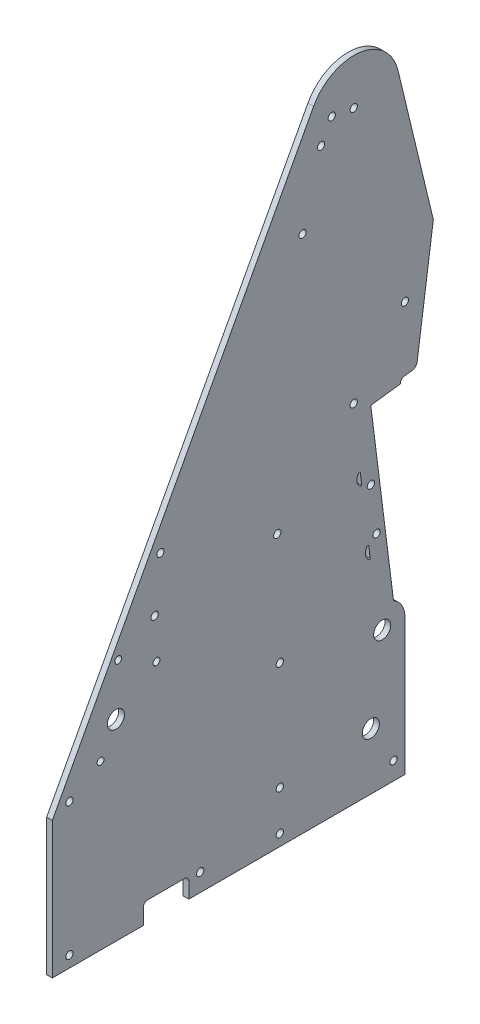
SolidWorks part; units mm, degrees
ref_plane "Front Plane" through (0, 0, 0) normal (0, 0, 1) x (1, 0, 0)
ref_plane "Top Plane" through (0, 0, 0) normal (0, 1, 0) x (1, 0, 0)
ref_plane "Right Plane" through (0, 0, 0) normal (1, 0, 0) x (0, 0, -1)
sketch "Sketch1" plane through (0, 0, 0) normal (1, 0, 0) x (0, 0, -1)
  line L0 (0, 0) -> (0, 76.2)
  line L6 (-19.05, 188.0016) -> (-2.512, 190.0852)
  line L7 (6.4943, 193.62) -> (15.875, 260.35)
  line L8 (15.875, 260.35) -> (-3.8791, 342.4892)
  line L9 (-50.965, 348.5436) -> (-196.85, 76.2)
  line L10 (-196.85, 0) -> (0, 0)
  line L11 (-196.85, 76.2) -> (-196.85, 0)
  line L12 (-19.05, 188.0016) -> (-6.35, 87.1985)
  line L13 (-0.4471, 192.7455) -> (6.4943, 193.62)
  line L14 (-2.512, 190.0852) -> (-3.1086, 194.8203) construction
  line L15 (-2.512, 190.0852) -> (6.1508, 191.1766) construction
  line L16 (6.1508, 191.1766) -> (6.4943, 193.62) construction
  arc A0 (-3.8791, 342.4892) -> (-50.965, 348.5436) centre (-28.575, 336.55) ccw
  arc A3 (0, 76.2) -> (-6.35, 87.1985) centre (-12.7, 76.2) ccw
  arc A4 (-2.512, 190.0852) -> (-0.4471, 192.7455) centre (-0.1494, 190.3829) cw
  dimension "D2" = 25.4
  dimension "D6" = 196.85
  dimension "D7" = 76.2
  dimension "D12" = 12.7
  dimension "D8" = 19.05
  dimension "D10" = 2.3813
  dimension "D1" = 28.575
  dimension "D3" = 336.55
  dimension "D4" = 25.4
  dimension "D5" = 101.6
  dimension "D9" = 6.35
  dimension ".5" = 12.7
  dimension "D11" = 76.2
  dimension "D13" = 76.2
  dimension "D14" = 15.875
  dimension "D15" = 6.35
extrude "Boss-Extrude1" add sketch "Sketch1" along normal blind 3.175
sketch "Sketch2" plane through (3.175, 0, 0) normal (1, 0, 0) x (0, 0, -1)
  line L16 (-146.05, 8.7909) -> (-146.05, -0.3034) construction
  line L17 (-123.0376, 11.1785) -> (-143.6624, 11.1785) construction
  line L18 (-120.65, -0.3034) -> (-120.65, 8.7909) construction
  line L19 (-146.05, 8.7909) -> (-146.05, 0)
  line L20 (-123.0376, 11.1785) -> (-143.6624, 11.1785)
  line L21 (-120.65, 0) -> (-120.65, 8.7909)
  line L25 (-146.05, 0) -> (-120.65, 0)
  line L26 (-196.85, 0) -> (0, 0) construction
  line L33 (-223.2996, 0) -> (-223.2996, 6.35) construction
  line L34 (-229.6496, 0) -> (-223.2996, 0) construction
  line L35 (-229.6496, 6.35) -> (-229.6496, 0) construction
  line L36 (-223.2996, 6.35) -> (-229.6496, 6.35) construction
  line L37 (-223.2996, 0) -> (-223.2996, 6.35)
  line L38 (-229.6496, 0) -> (-223.2996, 0)
  line L39 (-229.6496, 6.35) -> (-229.6496, 0)
  line L40 (-223.2996, 6.35) -> (-229.6496, 6.35)
  arc A0 (-143.6624, 11.1785) -> (-146.05, 8.7909) centre (-143.6624, 8.7909) ccw construction
  arc A1 (-120.65, 8.7909) -> (-123.0376, 11.1785) centre (-123.0376, 8.7909) ccw construction
  arc A2 (-143.6624, 11.1785) -> (-146.05, 8.7909) centre (-143.6624, 8.7909) ccw
  arc A3 (-120.65, 8.7909) -> (-123.0376, 11.1785) centre (-123.0376, 8.7909) ccw
extrude "Cut-Extrude1" cut sketch "Sketch2" against normal through all
sketch "Sketch3" plane through (3.175, 0, 0) normal (1, 0, 0) x (0, 0, -1)
  point P4 (-12.7, 76.2)
hole_wizard "3/8 Clearance Hole1" positions "Sketch3" profile "Sketch4" hole size "3/8" standard "ANSI Inch" end condition up to next
sketch "Sketch4" plane through (3.175, 76.2, 12.7) normal (0, 1, 0) x (0, 0, -1)
  line L0 (0, 0) -> (0, 3.175)
  line L1 (0, 3.175) -> (4.7625, 3.175)
  line L2 (4.7625, 3.175) -> (4.7625, 0)
  line L5 (4.7625, 0) -> (0, 0)
  line L11 (0, -6.35) -> (0, 107.95) construction
  dimension "Thru Hole Dia." = 9.525
  dimension "Thru Hole Depth" = 3.175
sketch "Sketch5" plane through (3.175, 0, 0) normal (1, 0, 0) x (0, 0, -1)
  line L0 (-12.7, 76.2) -> (19.6681, 37.0472)
  line L1 (19.6681, 37.0472) -> (18.4836, 24.56)
  line L2 (15.6221, 41.9413) -> (-25.2806, 17.5464)
  line L3 (-15.875, 19.05) -> (-25.2806, 17.5464)
  line L4 (0, 0) -> (0, 76.2) construction
  line L5 (-15.875, 19.05) -> (-27.0501, 3.6221)
  line L6 (-27.0501, 3.6221) -> (-54.7505, 169.5016)
  line L7 (50.8, 0) -> (50.8, 73.5762) construction
  dimension "D1" = 44.45
  dimension "D2" = 50.8
  dimension "D3" = 45
  dimension "D4" = 60.325
  dimension "D5" = 19.05
  dimension "D6" = 15.875
  dimension "D7" = 9.525
  dimension "D8" = 47.625
  dimension "D9" = 19.05
  dimension "D10" = 45
  dimension "D11" = 50.8
sketch "Sketch6" plane through (3.175, 0, 0) normal (1, 0, 0) x (0, 0, -1)
  circle A3 centre (-161.3885, 107.3015) radius 4.7625
  circle A5 centre (-161.3885, 107.3015) radius 6.985 construction
  circle A8 centre (-160.0862, 135.4185) radius 1.905 construction
  circle A9 centre (-138.7037, 123.9646) radius 1.905 construction
  arc A10 (-168.2338, 90.4891) -> (-169.0344, 93.0278) centre (-169.9339, 91.3486) ccw construction
  arc A11 (-169.0344, 93.0278) -> (-171.5914, 92.2876) centre (-169.9339, 91.3486) ccw construction
  arc A12 (-171.5914, 92.2876) -> (-168.2338, 90.4891) centre (-169.9339, 91.3486) ccw construction
  circle A17 centre (-160.0862, 135.4185) radius 1.905
  circle A18 centre (-138.7037, 123.9646) radius 1.905
  arc A19 (-168.2338, 90.4891) -> (-169.0344, 93.0278) centre (-169.9339, 91.3486) ccw
  arc A20 (-169.0344, 93.0278) -> (-171.5914, 92.2876) centre (-169.9339, 91.3486) ccw
  arc A21 (-171.5914, 92.2876) -> (-168.2338, 90.4891) centre (-169.9339, 91.3486) ccw
  dimension "D1" = 9.525
extrude "Cut-Extrude2" cut sketch "Sketch6" against normal through all
sketch "Sketch10" plane through (3.175, 0, 0) normal (1, 0, 0) x (0, 0, -1)
  circle A0 centre (-71.2566, 151.9429) radius 2.032
  dimension "D1" = 4.064
extrude "Cut-Extrude4" cut sketch "Sketch10" against normal through all
sketch "Sketch11" plane through (3.175, 0, 0) normal (1, 0, 0) x (0, 0, -1)
  circle A0 centre (-187.325, 80.5336) radius 2.032
  circle A1 centre (-187.325, 6.35) radius 2.032
  circle A2 centre (-187.325, 6.35) radius 2.032 construction
  circle A3 centre (-187.325, 80.5336) radius 2.032 construction
  dimension "D1" = 4.064
extrude "Cut-Extrude5" cut sketch "Sketch11" against normal through all
sketch "Sketch13" plane through (0, 0, 0) normal (-1, 0, 0) x (0, 0, 1)
  circle A0 centre (40.8349, 338.5416) radius 2.032
  circle A1 centre (46.8317, 327.3465) radius 2.032
  circle A2 centre (40.8349, 338.5416) radius 1.905 construction
  circle A3 centre (46.8317, 327.3465) radius 1.905 construction
  dimension "D1" = 4.064
extrude "Cut-Extrude6" cut sketch "Sketch13" against normal through all
sketch "Sketch14" plane through (3.175, 0, 0) normal (1, 0, 0) x (0, 0, -1)
  line L0 (-50.965, 348.5436) -> (-196.85, 76.2) construction
  line L1 (-136.525, 175.369) -> (-142.1225, 178.3674) construction
  circle A0 centre (-136.525, 175.369) radius 2.032
  dimension "D1" = 4.064
  dimension "D2" = 6.35
  dimension "D3" = 136.525
extrude "Cut-Extrude7" cut sketch "Sketch14" against normal through all
sketch "Sketch15" plane through (3.175, 0, 0) normal (1, 0, 0) x (0, 0, -1)
  circle A0 centre (-19.05, 31.75) radius 4.7625
  circle A1 centre (-12.7, 76.2) radius 4.7625 construction
  circle A2 centre (-28.575, 193.675) radius 2.032
  dimension "D1" = 44.45
  dimension "D3" = 4.064
  dimension "D2" = 6.35
  dimension "D4" = 161.925
  dimension "D5" = 9.525
extrude "Cut-Extrude8" cut sketch "Sketch15" against normal through all
sketch "Sketch16" plane through (3.175, 0, 0) normal (1, 0, 0) x (0, 0, -1)
  line L0 (-24.978, 158.8539) -> (-24.0851, 151.7662)
  line L1 (-6.35, 87.1985) -> (-19.05, 188.0016) construction
  line L2 (-20.2155, 121.0527) -> (-21.0031, 120.9535)
  line L3 (-24.978, 158.8539) -> (-25.7656, 158.7547)
  line L4 (-24.0851, 151.7662) -> (-24.8726, 151.667)
  line L5 (-12.7, 137.6001) -> (-26.6484, 135.8427) construction
  line L6 (-19.3226, 113.965) -> (-20.1101, 113.8658)
  line L7 (-19.3226, 113.965) -> (-20.2155, 121.0527)
  line L8 (-25.3253, 161.6102) -> (-23.7378, 149.0099) construction
  arc A0 (-25.7656, 158.7547) -> (-24.8726, 151.667) centre (-21.7352, 155.6624) ccw
  arc A1 (-20.1101, 113.8658) -> (-21.0031, 120.9535) centre (-16.9727, 117.8612) cw
  circle A2 centre (-19.0126, 149.6052) radius 2.032
  circle A3 centre (-15.8376, 124.4044) radius 2.032
  point P2 (-24.5315, 155.31)
  dimension "D2" = 0.7937
  dimension "D3" = 5.08
  dimension "D5" = 4.064
  dimension "D1" = 7.1437
  dimension "D4" = 38.1
  dimension "D6" = 4.7625
  dimension "D7" = 25.4
extrude "Cut-Extrude9" cut sketch "Sketch16" against normal up to next
fillet "Fillet1" radius 3.175 1 edges at (1.5875, 193.62, -6.4943)
sketch "Sketch17" plane through (3.175, 0, 0) normal (1, 0, 0) x (0, 0, -1)
  circle A0 centre (-6.35, 9.9085) radius 2.032
  circle A1 centre (-69.85, 6.35) radius 2.032
  circle A2 centre (-114.3, 9.9085) radius 2.032
  circle A3 centre (-114.3, 9.9085) radius 1.905 construction
  circle A4 centre (-69.85, 6.35) radius 2.286 construction
  circle A5 centre (-6.35, 9.9085) radius 1.905 construction
  circle A6 centre (-69.85, 28.575) radius 2.032
  circle A7 centre (-69.85, 28.575) radius 1.905 construction
  dimension "D1" = 4.064
extrude "Cut-Extrude10" cut sketch "Sketch17" against normal through all
sketch "Sketch18" plane through (0, 0, 0) normal (-1, 0, 0) x (0, 0, 1)
  line L0 (50.965, 348.5436) -> (196.85, 76.2) construction
  circle A0 centre (0, 228.6) radius 2.032
  circle A1 centre (69.85, 88.9) radius 2.032
  circle A2 centre (139.7, 146.5801) radius 2.032
  circle A3 centre (57.15, 289.9291) radius 2.032
  dimension "D1" = 4.064
  dimension "D2" = 228.6
  dimension "D4" = 17.145
  dimension "D5" = 139.7
  dimension "D6" = 22.225
  dimension "D7" = 57.15
  dimension "D8" = 69.85
  dimension "D9" = 88.9
extrude "Cut-Extrude11" cut sketch "Sketch18" against normal through all
sketch "Sketch19" plane through (0, 0, 0) normal (-1, 0, 0) x (0, 0, 1)
  circle A0 centre (28.575, 336.55) radius 2.032
  arc A1 (50.965, 348.5436) -> (3.8791, 342.4892) centre (28.575, 336.55) ccw construction
  dimension "D1" = 4.064
extrude "Cut-Extrude12" cut sketch "Sketch19" against normal through all
